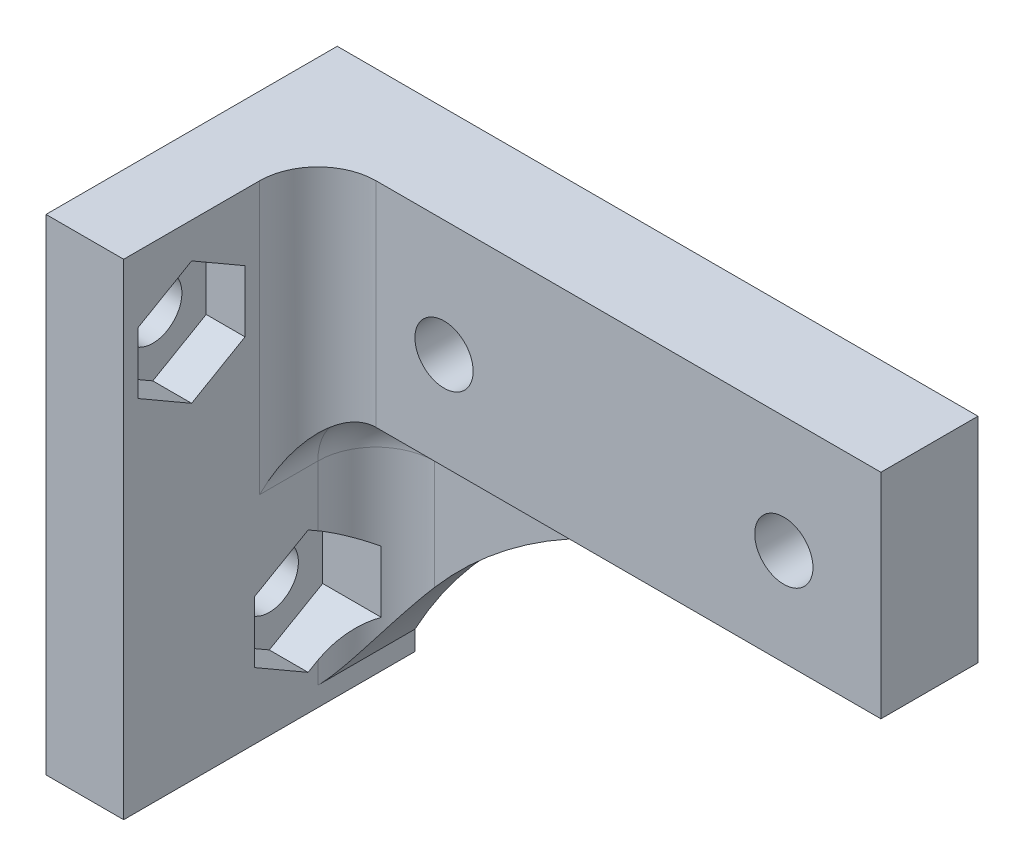
SolidWorks part; units mm, degrees
ref_plane "Alzado" through (0, 0, 0) normal (0, 0, 1) x (1, 0, 0)
ref_plane "Planta" through (0, 0, 0) normal (0, 1, 0) x (1, 0, 0)
ref_plane "Vista lateral" through (0, 0, 0) normal (1, 0, 0) x (0, 0, -1)
sketch "Croquis1" plane through (0, 0, 0) normal (0, 0, 1) x (1, 0, 0)
  line L1 (-11.25, -26.1) -> (-11.25, 8.2)
  line L3 (11.25, 8.2) -> (11.25, -26.1)
  line L16 (-10.75, 8.2) -> (-10.75, -26.6)
  line L17 (-10.75, -26.6) -> (-7, -26.6)
  line L18 (-7, -26.6) -> (-7, -37.6)
  line L19 (-7, -37.6) -> (7, -37.6)
  line L20 (7, -37.6) -> (7, -26.6)
  line L21 (7, -26.6) -> (10.75, -26.6)
  line L22 (10.75, -26.6) -> (10.75, 8.2)
  line L23 (8.25, 10.7) -> (-8.25, 10.7)
  line L26 (18.2779, -29.0343) -> (18.2779, 2.9657)
  line L27 (18.2779, 2.9657) -> (16.7779, 2.9657)
  line L28 (16.7779, 2.9657) -> (16.7779, -29.0343)
  line L29 (16.7779, -29.0343) -> (18.2779, -29.0343)
  line L34 (16.7779, -3.0343) -> (16.7779, 2.9657)
  line L35 (16.7779, 2.9657) -> (6.7779, 2.9657)
  line L36 (6.7779, 2.9657) -> (6.7779, -3.0343)
  line L37 (6.7779, -3.0343) -> (16.7779, -3.0343)
  line L42 (16.7779, -28.3343) -> (16.7779, -25.8343)
  line L43 (16.7779, -25.8343) -> (14.2779, -25.8343)
  line L44 (14.2779, -25.8343) -> (14.2779, -28.3343)
  line L45 (14.2779, -28.3343) -> (16.7779, -28.3343)
  line L54 (14.2779, -27.3343) -> (14.2779, -26.8343)
  line L55 (14.2779, -26.8343) -> (13.2779, -26.8343)
  line L56 (12.0279, -28.0843) -> (12.0279, -35.0843)
  line L57 (12.0279, -35.0843) -> (12.5279, -35.0843)
  line L58 (12.5279, -35.0843) -> (12.5279, -28.0843)
  line L59 (13.2779, -27.3343) -> (14.2779, -27.3343)
  line L60 (1.8, -2.0125) -> (1.8, 2.0125)
  line L61 (-1.8, 2.0125) -> (-1.8, -2.0125)
  circle A2 centre (0, 0) radius 12.85
  arc A6 (-8.25, 10.7) -> (-10.75, 8.2) centre (-8.25, 8.2) ccw
  arc A7 (10.75, 8.2) -> (8.25, 10.7) centre (8.25, 8.2) ccw
  circle A8 centre (-8.75, -20.6) radius 1.5
  circle A9 centre (8.75, -20.6) radius 1.5
  arc A14 (13.2779, -26.8343) -> (12.0279, -28.0843) centre (13.2779, -28.0843) ccw
  arc A15 (13.2779, -27.3343) -> (12.5279, -28.0843) centre (13.2779, -28.0843) ccw
  arc A18 (-1.8, -2.0125) -> (1.8, -2.0125) centre (0, 0) ccw
  arc A19 (1.8, 2.0125) -> (-1.8, 2.0125) centre (0, 0) ccw
sketch "Croquis2" plane through (0, 0, 0) normal (0, 0, 1) x (1, 0, 0)
  line L0 (-19.25, -14.6) -> (13.75, -14.6)
  line L1 (13.75, -14.6) -> (13.75, -25.6)
  line L2 (13.75, -14.6) -> (16.7779, -14.6) construction
  line L3 (-19.25, -14.6) -> (-19.25, -25.6)
  line L4 (-19.25, -25.6) -> (13.75, -25.6)
  line L5 (16.7779, 2.9657) -> (16.7779, -29.0343) construction
  line L6 (16.7779, -14.6) -> (16.7779, -25.6) construction
  line L8 (13.75, -25.6) -> (16.7779, -25.6) construction
  circle A0 centre (-8.75, -20.6) radius 1.5 construction
  circle A1 centre (-8.75, -20.6) radius 1.5
  circle A2 centre (8.75, -20.6) radius 1.5 construction
  circle A3 centre (8.75, -20.6) radius 1.5
  dimension "D4" = 5
  dimension "D1" = 5
  dimension "D2" = 6
  dimension "D3" = 10.5
extrude "Saliente-Extruir1" add sketch "Croquis2" along normal blind 5
sketch "Croquis3" plane through (0, 0, 0) normal (0, 0, 1) x (1, 0, 0)
  line L1 (-6, -19.0123) -> (-8.75, -17.4246)
  line L2 (-8.75, -17.4246) -> (-11.5, -19.0123)
  line L3 (-11.5, -19.0123) -> (-11.5, -22.1877)
  line L4 (-11.5, -22.1877) -> (-8.75, -23.7754)
  line L5 (-8.75, -23.7754) -> (-6, -22.1877)
  line L6 (-6, -22.1877) -> (-6, -19.0123)
  line L7 (11.9254, -20.6) -> (10.3377, -17.85)
  line L8 (10.3377, -17.85) -> (7.1623, -17.85)
  line L9 (7.1623, -17.85) -> (5.5746, -20.6)
  line L10 (5.5746, -20.6) -> (7.1623, -23.35)
  line L11 (7.1623, -23.35) -> (10.3377, -23.35)
  line L12 (10.3377, -23.35) -> (11.9254, -20.6)
  circle A0 centre (-8.75, -20.6) radius 2.75 construction
  circle A1 centre (8.75, -20.6) radius 2.75 construction
  dimension "D1" = 5.5
extrude "Cortar-Extruir1" cut sketch "Croquis3" along normal blind 2.5
sketch "Croquis5" plane through (0, 0, 0) normal (0, 0, 1) x (1, 0, 0)
  line L1 (-19.25, -14.6) -> (-15.25, -14.6)
  line L2 (-19.25, -14.6) -> (-19.25, -39.6)
  line L3 (-19.25, -39.6) -> (-15.25, -39.6)
  line L4 (-15.25, -14.6) -> (-15.25, -39.6)
  dimension "D1" = 4
  dimension "D2" = 25
extrude "Saliente-Extruir3" add sketch "Croquis5" along normal blind 15
sketch "Croquis7" plane through (0, 0, 0) normal (0, 0, -1) x (-1, 0, 0)
  line L1 (15.25, -25.6) -> (-13.75, -25.6) construction
  line L2 (15.25, -39.6) -> (15.25, -25.6) construction
  line L3 (15.25, -25.6) -> (-4.75, -25.6)
  line L4 (15.25, -38.6) -> (15.25, -25.6)
  arc A0 (-4.75, -25.6) -> (15.25, -38.6) centre (-6.7243, -50.5219) cw
  dimension "D3" = 25
  dimension "D1" = 20
  dimension "D2" = 13
extrude "Saliente-Extruir4" add sketch "Croquis7" against normal blind 2
sketch "Croquis6" plane through (-19.25, 0, 0) normal (-1, 0, 0) x (0, 0, 1)
  line L0 (5, -14.6) -> (5, -25.6) construction
  line L1 (5, -14.6) -> (5, -25.6) construction
  line L2 (0, -14.6) -> (15, -39.6) construction
  line L4 (5, -25.6) -> (0, -25.6) construction
  line L5 (0, -14.6) -> (0, -39.6) construction
  line L7 (15, -14.6) -> (15, -39.6) construction
  line L10 (11.5, -19.6) -> (5.5, -19.6) construction
  line L11 (11.5, -19.6) -> (11.5, -34.6) construction
  line L12 (11.5, -34.6) -> (5.5, -34.6) construction
  line L13 (5.5, -19.6) -> (5.5, -34.6) construction
  circle A0 centre (11.5, -19.6) radius 1.5
  circle A1 centre (5.5, -34.6) radius 1.5
  point P8 (11.5, -27.1)
  point P9 (7.5, -27.1)
  dimension "D1" = 3
  dimension "D2" = 15
  dimension "D3" = 6
  dimension "3" = 3.5
extrude "Cortar-Extruir2" cut sketch "Croquis6" against normal blind 12
sketch "Croquis8" plane through (-15.25, 0, 0) normal (1, 0, 0) x (0, 0, -1)
  line L1 (-11.5, -16.4246) -> (-14.25, -18.0123)
  line L2 (-14.25, -18.0123) -> (-14.25, -21.1877)
  line L3 (-14.25, -21.1877) -> (-11.5, -22.7754)
  line L4 (-11.5, -22.7754) -> (-8.75, -21.1877)
  line L5 (-8.75, -21.1877) -> (-8.75, -18.0123)
  line L6 (-8.75, -18.0123) -> (-11.5, -16.4246)
  line L7 (-8.25, -36.1877) -> (-5.5, -37.7754)
  line L8 (-5.5, -37.7754) -> (-2.75, -36.1877)
  line L9 (-2.75, -36.1877) -> (-2.75, -33.0123)
  line L10 (-2.75, -33.0123) -> (-5.5, -31.4246)
  line L11 (-5.5, -31.4246) -> (-8.25, -33.0123)
  line L12 (-8.25, -33.0123) -> (-8.25, -36.1877)
  circle A0 centre (-11.5, -19.6) radius 2.75 construction
  circle A1 centre (-5.5, -34.6) radius 2.75 construction
  dimension "D1" = 5.5
extrude "Cortar-Extruir3" cut sketch "Croquis8" against normal blind 2
fillet "Redondeo1" radius 3 4 edges at (-5.25, -25.6, 2) (-15.25, -32.1, 2) (-15.25, -25.6, 3.5) (-15.25, -20.1, 5)
